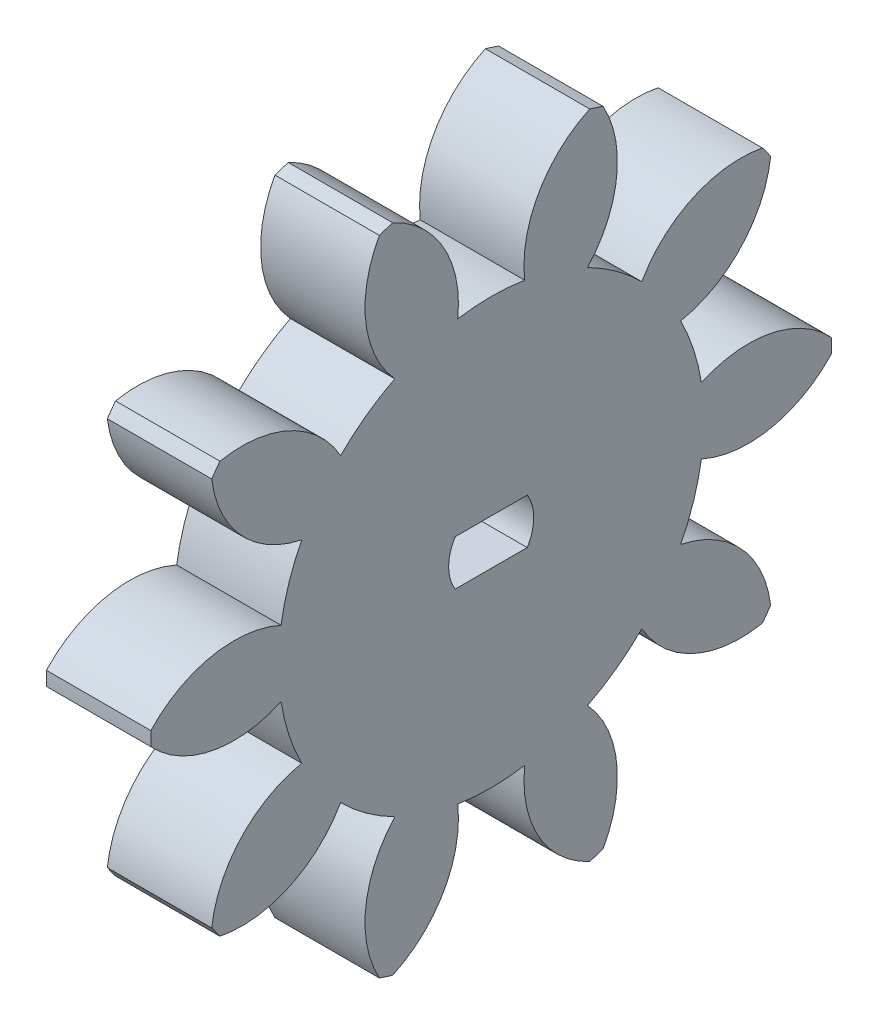
SolidWorks part; units mm, degrees
ref_plane "Plane1" through (0, 0, 0) normal (0, 0, 1) x (1, 0, 0)
ref_plane "Plane2" through (0, 0, 0) normal (0, 1, 0) x (1, 0, 0)
ref_plane "Plane3" through (0, 0, 0) normal (1, 0, 0) x (0, 0, -1)
sketch "HoldingSke" plane through (0, 0, 0) normal (0, 1, 0) x (1, 0, 0)
  line L0 (0, 0) -> (200.1129, -35.2853)
  line L1 (-15, 0) -> (100, 0) construction
  line L2 (0, 0) -> (-2.1039, 2.3779)
  line L3 (0, 0) -> (-11.863, 4.5341)
  line L4 (0, 0) -> (8.5048, 1.4996)
  line L5 (0, 0) -> (-47.5972, -17.7524)
  line L6 (0, 0) -> (-4.8428, -3.2675)
  line L7 (-2.1039, 2.3779) -> (8.8308, 51.9871)
  line L8 (-76.2, 54.61) -> (-71.1708, 54.61)
  line L9 (-71.009, 38.7566) -> (-53.1078, 45.2721)
  line L10 (-76.2, 71.12) -> (104.1128, 71.12)
  line L11 (0, 0) -> (-5.842, 0)
  line L12 (-76.2, 101.6) -> (-76.0857, 101.6)
  line L13 (24.9733, 27.94) -> (52.9518, 28.4284)
  line L14 (24.9733, 27.94) -> (24.9746, 27.94)
  line L15 (24.9733, 27.94) -> (100.4006, 29.5858)
  circle A0 centre (0, 0) radius 2.3812
  circle A1 centre (0, 0) radius 11.905
  circle A2 centre (0, 0) radius 38.1
  circle A3 centre (0, 0) radius 2.3812
  dimension "Num_teeth" = 10
  dimension "H" = 19.05
  dimension "Pitch_radius" = 180.3128
  dimension "Width" = 5.842
  dimension "Thickness" = 5.842
sketch "BasProSke" plane through (0, 0, 0) normal (0, 1, 0) x (1, 0, 0)
  line L0 (-10, 0) -> (60, 0) construction
  line L1 (0, 0) -> (0, 19.05)
  line L2 (0, 0) -> (5.842, 0)
  line L3 (5.842, 0) -> (5.842, 19.05)
  line L4 (5.842, 19.05) -> (0, 19.05)
  dimension "Thickness" = 5.842
  dimension "Diameter" = 38.1
revolve "Base-Revolve" add sketch "BasProSke" angle 360 about L0
sketch "TooCutSke" plane through (0, 0, 0) normal (1, 0, 0) x (0, 0, -1)
  line L1 (0, 0) -> (0, 107) construction
  line L2 (0, 0) -> (-2.683, 15.6466) construction
  line L3 (0, 0) -> (-9.7093, 29.8821) construction
  line L4 (-2.683, 15.6466) -> (-4.8546, 14.941) construction
  arc A0 (1.8735, 11.7566) -> (-1.8735, 11.7566) centre (0, 0) ccw
  arc A1 (5.5485, 18.2506) -> (-5.5485, 18.2506) centre (0, 0) ccw
  circle A2 centre (0, 0) radius 15.875 construction
  circle A3 centre (0, 0) radius 14.9176 construction
  arc A4 (-1.8735, 11.7566) -> (-5.5485, 18.2506) centre (-8.183, 12.4729) ccw
  arc A5 (5.5485, 18.2506) -> (1.8735, 11.7566) centre (8.183, 12.4729) ccw
extrude "ToothCut" cut sketch "TooCutSke" along normal through all
fillet "Breaks" [suppressed] radius 0.0635 tangent propagation no
fillet "RootFillets" [suppressed] radius 0.795
pattern_circular "TeethCuts" count 10 every 36 about axis through (-10, 0, 0) along (1, 0, 0) of "ToothCut", "RootFillets", "Breaks"
sketch "HubNeaOneSke" plane through (0, 0, 0) normal (-1, 0, 0) x (0, 0, 1)
  circle A0 centre (0, 0) radius 11.905
  dimension "Diameter" = 23.81
extrude "HubNearOne" [suppressed] add sketch "HubNeaOneSke" along normal blind 44.9581
sketch "HubNeaBotSke" plane through (0, 0, 0) normal (-1, 0, 0) x (0, 0, 1)
  circle A0 centre (0, 0) radius 11.905
  dimension "Diameter" = 23.81
extrude "HubNearBoth" [suppressed] add sketch "HubNeaBotSke" along normal blind 22.479
ref_plane "FarPln" through (5.842, 0, 0) normal (1, 0, 0) x (0, 0, -1)
sketch "HubFarSke" plane through (5.842, 0, 0) normal (1, 0, 0) x (0, 0, -1)
  circle A0 centre (0, 0) radius 11.905
  dimension "Diameter" = 23.81
extrude "HubFar" [suppressed] add sketch "HubFarSke" along normal blind 22.479
sketch "BorSke" plane through (0, 0, 0) normal (1, 0, 0) x (0, 0, -1)
  circle A0 centre (0, 0) radius 2.3812
  dimension "Diameter" = 4.7625
extrude "Bore" cut sketch "BorSke" along normal mid plane 101.6001
sketch "KeySke" plane through (0, 0, 0) normal (1, 0, 0) x (0, 0, -1)
  line L0 (-0.127, 0) -> (-0.127, 2.6479)
  line L1 (-0.127, 2.6479) -> (0.127, 2.6479)
  line L2 (0.127, 2.6479) -> (0.127, 0)
  line L3 (0, 0) -> (0, 34) construction
  line L4 (-0.127, 0) -> (0.127, 0)
  dimension "Width" = 0.254
extrude "Keyway" [suppressed] cut sketch "KeySke" along normal mid plane 101.6001
pattern_circular "Keyway2" [suppressed] count 2 every 90 about axis through (-10, 0, 0) along (1, 0, 0) reverse direction yes
sketch "Sketch1" plane through (5.842, 0, 0) normal (1, 0, 0) x (0, 0, -1)
  line L0 (-4.4067, 4.572) -> (4.4067, 4.572)
  arc A0 (4.4067, 4.572) -> (-4.4067, 4.572) centre (0, 0) ccw
  point P5 (0, -6.35)
  dimension "D1" = 10.922
extrude "Boss-Extrude1" add sketch "Sketch1" against normal up to surface (5.842 mm away) up to face at (0, 0, -2.3812)
sketch "Sketch2" plane through (5.842, 0, 0) normal (1, 0, 0) x (0, 0, -1)
  line L0 (-2.177, 1.27) -> (2.177, 1.27)
  line L1 (-2.177, -1.27) -> (2.177, -1.27)
  line L2 (0, 1.27) -> (0, -1.27) construction
  arc A0 (-2.177, -1.27) -> (2.177, -1.27) centre (0, 0) ccw
  arc A1 (2.177, 1.27) -> (-2.177, 1.27) centre (0, 0) ccw
  point P10 (0, 0)
  dimension "D1" = 2.54
extrude "Boss-Extrude3" add sketch "Sketch2" against normal up to surface (5.842 mm away) up to face at (0, 0, -2.3812)
equation "' \"Pitch@HoldingSke\" = 4"
equation "' \"Num_teeth@HoldingSke\" = 12"
equation "' \"Ap@HoldingSke\" =  20"
equation "' \"Ap@HoldingSke\" = 20"
equation "' \"Width@HoldingSke\" = 0.5"
equation "' \"Hub_dia@HoldingSke\"= 1"
equation "' \"Hub_dia@HoldingSke\" = 1"
equation "' \"Overall_len@HoldingSke\" = 1.0"
equation "' \"Bore@HoldingSke\" = 0.75"
equation "' \"T_dim@HoldingSke\" = 0.85"
equation "' \"Width@KeySke\" = 0.25"
equation "' \"Show_teeth@HoldingSke\" = 13"
equation "' \"Backlash@HoldingSke\" = 0.009"
equation "' \"Addendum_fac@HoldingSke\" = 1.0"
equation "' \"Dedendum_fac@HoldingSke\" = 1.25"
equation "' \"Dedendum_add@HoldingSke\" = 0.00005"
equation "' \"Clearance_fac@HoldingSke\" = 0.25"
equation "' \"Pitch@HoldingSke\" = 0.5"
equation "' \"Num_teeth@HoldingSke\" = 23"
equation "' \"Show_teeth@HoldingSke\" = 23"
equation "' \"Backlash@HoldingSke\" = 0.0375"
equation "\"Overcut_dia@TooCutSke\" = (\"Num_teeth@HoldingSke\" + 2 * \"Addendum_fac@HoldingSke\") / \"Pitch@HoldingSke\" + 0.002"
equation "\"Pitch_dia@TooCutSke\" = \"Num_teeth@HoldingSke\" / \"Pitch@HoldingSke\""
equation "\"Base_dia@TooCutSke\" = \"Num_teeth@HoldingSke\" / \"Pitch@HoldingSke\" * cos((\"Ap@HoldingSke\"  * 3.14159265 / 180))"
equation "\"Root_dia@TooCutSke\" = (\"Num_teeth@HoldingSke\" + 2) / \"Pitch@HoldingSke\" - 2 * (\"Addendum_fac@HoldingSke\" + \"Dedendum_fac@HoldingSke\") / \"Pitch@HoldingSke\" - \"Dedendum_add@HoldingSke\" * 2"
equation "\"Half_ang@TooCutSke\" = 180 / \"Num_teeth@HoldingSke\""
equation "\"Half_CT@TooCutSke\" = \"Num_teeth@HoldingSke\" / \"Pitch@HoldingSke\" * sin((3.14159265 / 2 / \"Num_teeth@HoldingSke\")) / 2 - 7 * \"Backlash@HoldingSke\" / 4"
equation "\"Flank_rad@TooCutSke\" = \"Num_teeth@HoldingSke\" / \"Pitch@HoldingSke\" / 5"
equation "\"Radius@RootFillets\" = \"Clearance_fac@HoldingSke\" / \"Pitch@HoldingSke\" + \"Dedendum_add@HoldingSke\""
equation "\"Break_rad@Breaks\" = 0.02 / \"Pitch@HoldingSke\""
equation "\"Thickness@HoldingSke\" = \"Width@HoldingSke\""
equation "\"OAL@HoldingSke\" = \"Thickness@HoldingSke\""
equation "\"MHD@HoldingSke\" = (\"Num_teeth@HoldingSke\" + 2) / \"Pitch@HoldingSke\" - 2 * (\"Addendum_fac@HoldingSke\" + \"Dedendum_fac@HoldingSke\")  / \"Pitch@HoldingSke\" - \"Dedendum_add@HoldingSke\" * 2"
equation "\"MBD@HoldingSke\" = (\"Num_teeth@HoldingSke\" + 2) / \"Pitch@HoldingSke\" - 2 * (\"Addendum_fac@HoldingSke\" + \"Dedendum_fac@HoldingSke\")  / \"Pitch@HoldingSke\" - \"Dedendum_add@HoldingSke\" * 2 - 0.002"
equation "\"MHD@HoldingSke\" = ((sgn( \"MHD@HoldingSke\" - \"Hub_dia@HoldingSke\" )-1)*( \"MHD@HoldingSke\" - \"Hub_dia@HoldingSke\" ))/-2+ \"Hub_dia@HoldingSke\""
equation "\"MBD@HoldingSke\" = ((sgn( \"MBD@HoldingSke\" - \"Bore@HoldingSke\" )-1)*( \"MBD@HoldingSke\" - \"Bore@HoldingSke\" ))/-2+ \"Bore@HoldingSke\""
equation "\"OAL@HoldingSke\" = ((sgn( \"OAL@HoldingSke\" - \"Overall_len@HoldingSke\" )+1)*( \"OAL@HoldingSke\" - \"Overall_len@HoldingSke\" ))/2 + \"Overall_len@HoldingSke\" + 0.000002"
equation "\"Num_teeth@TeethCuts\" = int( \"Show_teeth@HoldingSke\" ) + 1"
equation "\"Num_teeth@TeethCuts\" = ((sgn( \"Num_teeth@TeethCuts\" - \"Num_teeth@HoldingSke\" )-1)*( \"Num_teeth@TeethCuts\" - \"Num_teeth@HoldingSke\" ))/-2+ \"Num_teeth@HoldingSke\""
equation "\"Num_teeth@TeethCuts\" = ((sgn( \"Num_teeth@TeethCuts\" - 2.0)+1)*( \"Num_teeth@TeethCuts\" - 2.0))/2 +2.0"
equation "\"Angle@TeethCuts\" = 360.0 / \"Num_teeth@HoldingSke\""
equation "\"Diameter@BasProSke\" = (\"Num_teeth@HoldingSke\" + 2 * \"Addendum_fac@HoldingSke\") / \"Pitch@HoldingSke\""
equation "\"Thickness@BasProSke\"  = \"Thickness@HoldingSke\""
equation "' \"Fillet_rad@BasProSke\" =  \"Thickness@HoldingSke\" * 0.05"
equation "' \"Fillet_rad@BasProSke\" = \"Thickness@HoldingSke\" * 0.05"
equation "\"MHD@HoldingSke\" = ((sgn( \"MHD@HoldingSke\" - \"Root_dia@TooCutSke\" )-1)*( \"MHD@HoldingSke\" - \"Root_dia@TooCutSke\" ))/-2+ \"Root_dia@TooCutSke\""
equation "\"Diameter@HubNeaOneSke\" = \"MHD@HoldingSke\""
equation "\"Length@HubNearOne\" = \"OAL@HoldingSke\" - \"Thickness@BasProSke\""
equation "\"Diameter@HubNeaBotSke\" = \"MHD@HoldingSke\""
equation "\"Length@HubNearBoth\" = ( \"OAL@HoldingSke\" - \"Thickness@BasProSke\" ) / 2.0"
equation "\"Thickness@FarPln\" = \"Thickness@BasProSke\""
equation "\"Diameter@HubFarSke\" = \"MHD@HoldingSke\""
equation "\"Length@HubFar\" = ( \"OAL@HoldingSke\" - \"Thickness@BasProSke\" ) / 2.0"
equation "\"Diameter@BorSke\" = \"MBD@HoldingSke\""
equation "\"D1@Bore\" = \"OAL@HoldingSke\" * 2.0"
equation "\"D1@Keyway\" = \"OAL@HoldingSke\" * 2.0"
equation "\"Offset@KeySke\" = \"T_dim@HoldingSke\" - \"MBD@HoldingSke\" / 2.0"
